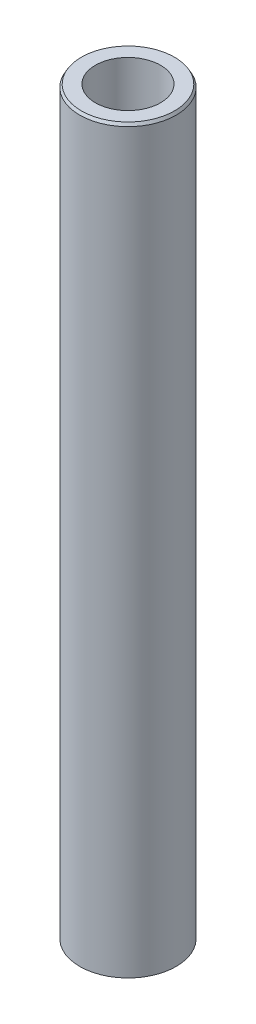
SolidWorks part; units mm, degrees
ref_plane "Front Plane" through (0, 0, 0) normal (0, 0, 1) x (1, 0, 0)
ref_plane "Top Plane" through (0, 0, 0) normal (0, 1, 0) x (1, 0, 0)
ref_plane "Right Plane" through (0, 0, 0) normal (1, 0, 0) x (0, 0, -1)
sketch "Sketch1" plane through (0, 0, 0) normal (0, 1, 0) x (1, 0, 0)
  circle A0 centre (0, 0) radius 32.5
  dimension "SHAFT_OD" = 65
extrude "Boss-Extrude1" add sketch "Sketch1" along normal blind 500.0569
sketch "Sketch2" plane through (0, 0, 0) normal (0, 1, 0) x (1, 0, 0)
  circle A0 centre (0, 0) radius 21.9658
  dimension "BORE_D" = 43.9316
extrude "Cut-Extrude1" cut sketch "Sketch2" along normal through all
chamfer "Chamfer1" distance 1.9252 angle 30 2 edges at (0, 500.0569, 32.5) (0, 0, 32.5) first distance on face at (0, 500.0569, 32.5) first distance on face at (0, 0, 21.9658)
